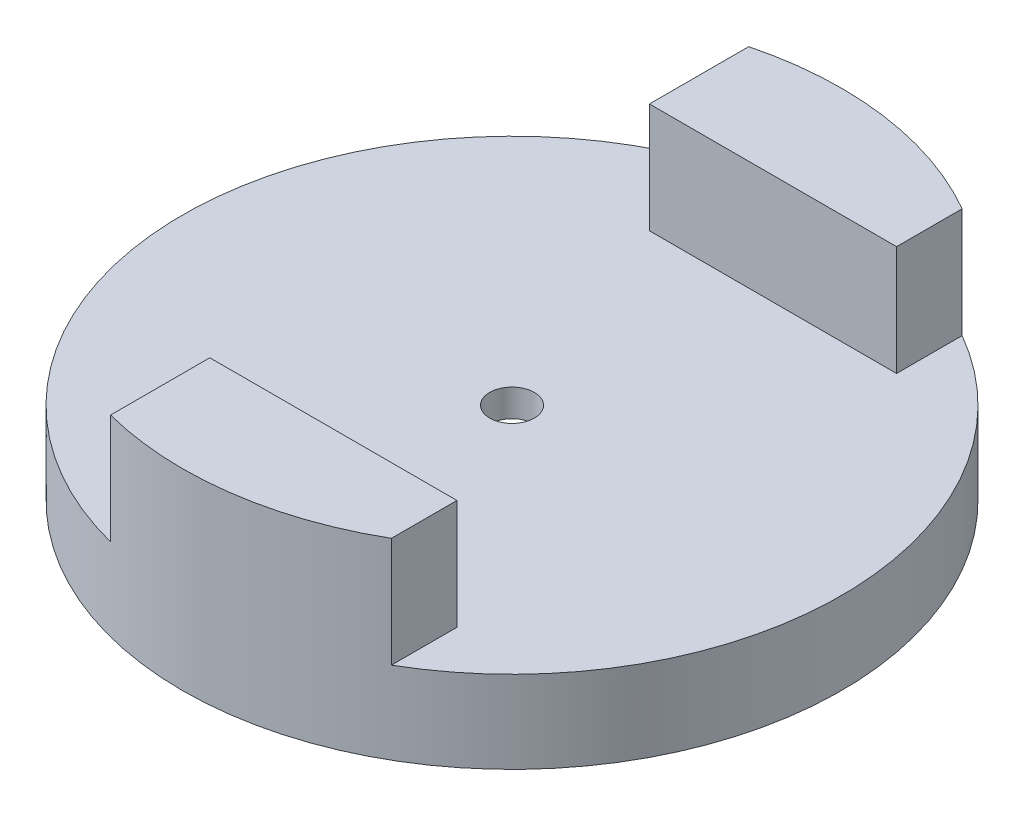
SolidWorks part; units mm, degrees
material "1023 Carbon Steel Sheet (SS)"
ref_plane "Front Plane" through (0, 0, 0) normal (0, 0, 1) x (1, 0, 0)
ref_plane "Top Plane" through (0, 0, 0) normal (0, 1, 0) x (1, 0, 0)
ref_plane "Right Plane" through (0, 0, 0) normal (1, 0, 0) x (0, 0, -1)
sketch "Sketch1" plane through (0, 0, 0) normal (0, 1, 0) x (1, 0, 0)
  line L0 (-19.05, -73.7803) -> (-19.05, -50.8305)
  line L1 (-19.05, -50.8305) -> (38.1, -50.8305)
  line L2 (38.1, -50.8305) -> (38.1, -65.9911)
  line L3 (0, 0) -> (-76.2, 0) construction
  line L4 (38.1, 50.8305) -> (38.1, 65.9911)
  line L5 (-19.05, 50.8305) -> (38.1, 50.8305)
  line L6 (-19.05, 73.7803) -> (-19.05, 50.8305)
  line L7 (-19.05, -63.5305) -> (38.1, -63.5305) construction
  line L8 (0, 0) -> (0, -63.5305) construction
  circle A0 centre (0, 0) radius 76.2
  circle A1 centre (0, 0) radius 74.1401
  circle A2 centre (0, 0) radius 5.1594
  dimension "D1" = 152.4
  dimension "D2" = 148.2801
  dimension "D6" = 10.3187
  dimension "D4" = 63.5305
  dimension "D5" = 12.7
  dimension "D7" = 19.05
  dimension "D3" = 38.1
extrude "Boss-Extrude1" add sketch "Sketch1" against normal blind 6.35 contours L2 A1 L4 L5 L6 L0 L1 | A1 L6 A0 L0 | A1 L0 A0 L2 | L0 A1 L2 L1 | L4 A1 L6 L5 | A1 L4 A0 L6 region at (-74.6176, 0, 0) region at (-18.4648, 0, 72.7156) region at (-72.078, 0, 0) region at (7.7413, 0, 61.4073) region at (10.2114, 0, -74.9221) region at (7.7413, 0, -61.4073)
extrude "Boss-Extrude2" add sketch "Sketch1<3>" against normal blind 19.05 contours A1 L6 A0 L0 | A1 L4 A0 L6 | A1 L2 A0 L4 | A1 L0 A0 L2 region at (-74.6176, 0, 0) region at (-18.4648, 0, 72.7156) region at (10.2114, 0, -74.9221) region at (39.4737, 0, 64.7963)
sketch "Sketch1<3>" plane through (0, 0, 0) normal (0, 1, 0) x (1, 0, 0) same geometry as "Sketch1"
extrude "Boss-Extrude3" add sketch "Sketch1<4>" along normal blind 25.4 contours A1 L4 A0 L6 | L4 A1 L6 L5 | L0 A1 L2 L1 | A1 L0 A0 L2 region at (-18.4648, 0, 72.7156) region at (7.7413, 0, 61.4073) region at (10.2114, 0, -74.9221) region at (7.7413, 0, -61.4073)
sketch "Sketch1<4>" plane through (0, 0, 0) normal (0, 1, 0) x (1, 0, 0) same geometry as "Sketch1"
hole_wizard "Pipe Tap Drill for 3/8 Tap1" positions "3DSketch1" profile "Sketch4" hole size "3/8" standard "ANSI Inch"
sketch3d "3DSketch1"
  line L0 (-19.05, 12.7, -63.5305) -> (-19.05, 12.7, -50.8305) construction
  line L1 (-19.05, 25.4, -50.8305) -> (-19.05, 0, -50.8305) construction
  line L3 (-19.05, 12.7, 50.8305) -> (-19.05, 12.7, 63.5305) construction
  line L4 (-19.05, 25.4, 50.8305) -> (-19.05, 0, 50.8305) construction
  point P0 (-19.05, 12.7, -63.5305)
  point P2 (-19.05, 12.7, 63.5305)
  point P15 (-19.05, 12.7, 68.8623)
  dimension "D1" = 12.7
sketch "Sketch4" plane through (-19.05, 12.7, -63.5305) normal (0, 1, 0) x (0, 0, 1)
  line L0 (0, 0) -> (0, 34.7686)
  line L1 (0, 34.7686) -> (7.1374, 30.48)
  line L2 (7.1374, 30.48) -> (7.1374, 0)
  line L5 (7.1374, 0) -> (0, 0)
  line L10 (0, 34.7686) -> (-7.1374, 30.48) construction
  line L11 (0, -6.35) -> (0, 107.95) construction
  dimension "Hole Dia." = 14.2748
  dimension "Hole Depth" = 30.48
  dimension "Drill Angle" = 118
equation "\"D2@Sketch1\"=2*(\"rotor tip@[TP] [Turb] Turbine.Assembly\"+\"rotor clearance@[TP] [Turb] Turbine.Assembly\")"
equation "\"D4@Sketch1\"=\"rotor pitchline@[TP] [Turb] Turbine.Assembly\""
